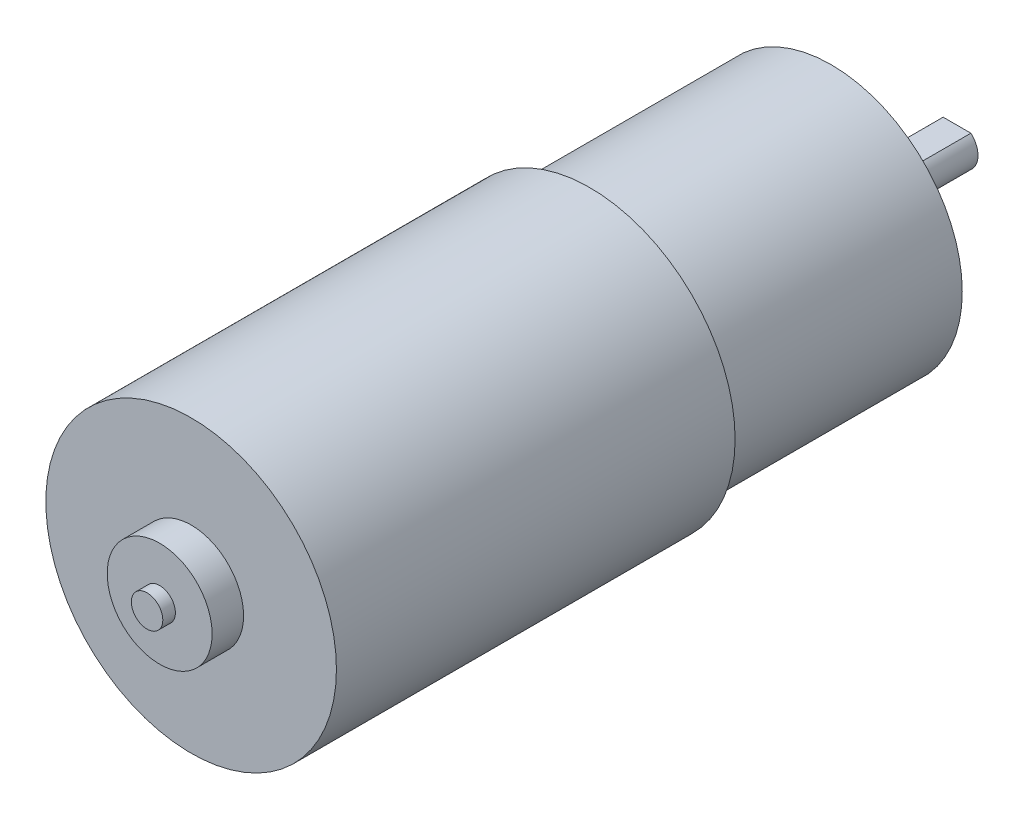
SolidWorks part; units mm, degrees
material "6063-T6"
ref_plane "Front Plane" through (0, 0, 0) normal (0, 0, 1) x (1, 0, 0)
ref_plane "Top Plane" through (0, 0, 0) normal (0, 1, 0) x (1, 0, 0)
ref_plane "Right Plane" through (0, 0, 0) normal (1, 0, 0) x (0, 0, -1)
sketch "Sketch1" plane through (0, 0, 0) normal (0, 0, 1) x (1, 0, 0)
  circle A0 centre (0, 0) radius 12.5
  dimension "D1" = 25
extrude "Boss-Extrude1" add sketch "Sketch1" along normal blind 23
sketch "Sketch2" plane through (0, 0, 23) normal (0, 0, 1) x (1, 0, 0)
  circle A0 centre (0, 0) radius 13.85
  dimension "D1" = 27.7
extrude "Boss-Extrude2" add sketch "Sketch2" along normal blind 38
sketch "Sketch3" plane through (0, 0, 61) normal (0, 0, 1) x (1, 0, 0)
  circle A0 centre (0, 0) radius 5
  dimension "D1" = 10
extrude "Boss-Extrude3" add sketch "Sketch3" along normal blind 3
sketch "Sketch4" plane through (0, 0, 64) normal (0, 0, 1) x (1, 0, 0)
  circle A0 centre (0, 0) radius 1.5
  dimension "D1" = 3
extrude "Boss-Extrude4" add sketch "Sketch4" along normal blind 1.2
sketch "Sketch5" plane through (0, 0, 0) normal (0, 0, 1) x (1, 0, 0)
  circle A0 centre (0, 0) radius 3.5
  dimension "D1" = 7
extrude "Boss-Extrude5" add sketch "Sketch5" against normal blind 2.5
sketch "Sketch6" plane through (0, 0, -2.5) normal (0, 0, -1) x (-1, 0, 0)
  circle A0 centre (0, 0) radius 2
  dimension "D1" = 4
extrude "Boss-Extrude6" add sketch "Sketch6" along normal blind 9.5
sketch "Sketch7" plane through (0, 0, -12) normal (0, 0, -1) x (-1, 0, 0)
  line L0 (-1.3229, 1.5) -> (1.3229, 1.5)
  circle A1 centre (0, 0) radius 2
  arc A2 (1.3229, 1.5) -> (-1.3229, 1.5) centre (0, 0) ccw
  point P5 (0, 1.5)
  dimension "D2" = 1.5
  dimension "D1" = 0
extrude "Cut-Extrude1" cut sketch "Sketch7" against normal blind 8
sketch "Sketch8" plane through (0, 0, 0) normal (0, 0, -1) x (-1, 0, 0)
  line L0 (0, 0) -> (12.5, 0) construction
  line L1 (0, 0) -> (-12.5, 0) construction
  line L2 (0, 0) -> (0, 12.5) construction
  line L3 (0, 0) -> (0, -12.5) construction
  circle A0 centre (0, 0) radius 12.5 construction
  circle A3 centre (0, 0) radius 12.5 construction
  circle A4 centre (0, 8.5) radius 1.5
  circle A5 centre (0, -8.5) radius 1.5
  dimension "D2" = 3
  dimension "D1" = 17
extrude "Cut-Extrude3" cut sketch "Sketch8" against normal blind 6.5
thread "Thread2" pitch 0.5 method cut profile "Thread Profile2" start angle 0, offset 0, length 0, pitch 0.5, diameter 3
ref_plane "Plane2" through (1.5, -8.5, 0) normal (0, -1, 0) x (1, 0, 0)
sketch "Thread Profile2" plane through (1.5, -8.5, 0) normal (0, -1, 0) x (1, 0, 0)
  line L0 (0, 0) -> (0, 0.5) construction
  line L1 (0, 0) -> (0.2706, 0.1562)
  line L2 (0.2706, 0.1562) -> (0.2706, 0.2187)
  line L3 (0.2706, 0.2187) -> (0, 0.375)
  line L4 (0.2706, 0.1875) -> (0, 0.1875) construction
  line L11 (0, 0) -> (0, 0.375)
  point P2 (0, 0)
  dimension "Pitch" = 0.5
  dimension "Profile_Angle" = 60
  dimension "Profile_Land" = 0.0625
  dimension "Profile_Height" = 0.2706
thread "Thread3" pitch 0.5 method cut profile "Thread Profile3" start angle 0, offset 0, length 0, pitch 0.5, diameter 3
ref_plane "Plane3" through (1.5, 8.5, 0) normal (0, -1, 0) x (1, 0, 0)
sketch "Thread Profile3" plane through (1.5, 8.5, 0) normal (0, -1, 0) x (1, 0, 0)
  line L0 (0, 0) -> (0, 0.5) construction
  line L1 (0, 0) -> (0.2706, 0.1562)
  line L2 (0.2706, 0.1562) -> (0.2706, 0.2187)
  line L3 (0.2706, 0.2187) -> (0, 0.375)
  line L4 (0.2706, 0.1875) -> (0, 0.1875) construction
  line L11 (0, 0) -> (0, 0.375)
  point P2 (0, 0)
  dimension "Pitch" = 0.5
  dimension "Profile_Angle" = 60
  dimension "Profile_Land" = 0.0625
  dimension "Profile_Height" = 0.2706
